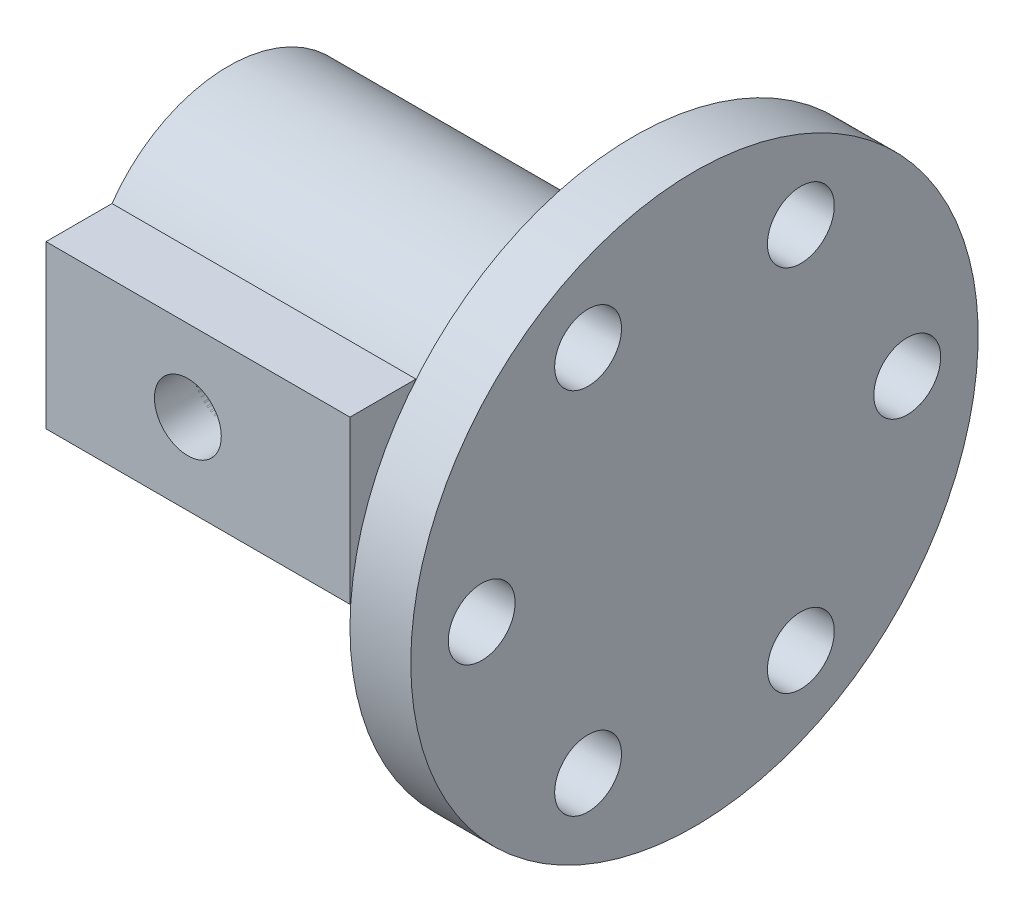
SolidWorks part; units mm, degrees
ref_plane "Front Plane" through (0, 0, 0) normal (0, 0, 1) x (1, 0, 0)
ref_plane "Top Plane" through (0, 0, 0) normal (0, 1, 0) x (1, 0, 0)
ref_plane "Right Plane" through (0, 0, 0) normal (1, 0, 0) x (0, 0, -1)
sketch "Sketch1" plane through (0, 0, 0) normal (0, 1, 0) x (1, 0, 0)
  line L0 (0, 0) -> (23, 0) construction
  line L1 (0, 0) -> (0, 7)
  line L2 (0, 7) -> (20, 7)
  line L3 (20, 7) -> (20, 14)
  line L4 (20, 14) -> (23, 14)
  line L5 (23, 14) -> (23, 0)
  line L6 (0, 0) -> (23, 0)
  dimension "D1" = 20
  dimension "D2" = 3
  dimension "D3" = 14
  dimension "D4" = 7
revolve "Revolve1" add sketch "Sketch1" angle 360 about L6
sketch "Sketch2" plane through (20, 0, 0) normal (-1, 0, 0) x (0, 0, 1)
  circle A0 centre (0, 0) radius 10.5 construction
  circle A1 centre (10.5, 0) radius 1.65
  circle A2 centre (5.25, -9.0933) radius 1.65
  circle A3 centre (-5.25, -9.0933) radius 1.65
  circle A4 centre (-10.5, 0) radius 1.65
  circle A5 centre (-5.25, 9.0933) radius 1.65
  circle A6 centre (5.25, 9.0933) radius 1.65
  point P17 (0, 0)
  dimension "D1" = 21
  dimension "D2" = 3.3
  dimension "D3" = 6
extrude "Cut-Extrude1" cut sketch "Sketch2" against normal up to next
sketch "Sketch4" plane through (0, 0, 0) normal (-1, 0, 0) x (0, 0, 1)
  circle A0 centre (0, 0) radius 3.15
  dimension "D1" = 6.3
extrude "Cut-Extrude2" cut sketch "Sketch4" against normal blind 13
ref_plane "Plane1" through (0, 0, 7) normal (0, 0, 1) x (1, 0, 0)
sketch "Sketch5" plane through (0, 0, 7) normal (0, 0, 1) x (1, 0, 0)
  circle A0 centre (7, 0) radius 1.65
  dimension "D1" = 3.3
  dimension "D2" = 7
extrude "Cut-Extrude4" cut sketch "Sketch5" against normal blind 6
sketch "Sketch6" plane through (0, 0, 7) normal (0, 0, 1) x (1, 0, 0)
  line L0 (0, 7) -> (0, -7) construction
  line L1 (0, 4) -> (15, 4)
  line L2 (0, 4) -> (0, -4)
  line L3 (0, -4) -> (15, -4)
  line L4 (15, 4) -> (15, -4)
  circle A0 centre (7, 0) radius 1.65 construction
  circle A1 centre (7, 0) radius 1.65
  dimension "D1" = 15
  dimension "D2" = 4
  dimension "D3" = 4
fillet "Fillet1" radius 1 1 edges at (20, 0, 7)
extrude "Boss-Extrude1" add sketch "Sketch6" along normal blind 2 and the other way blind 2 separate body
